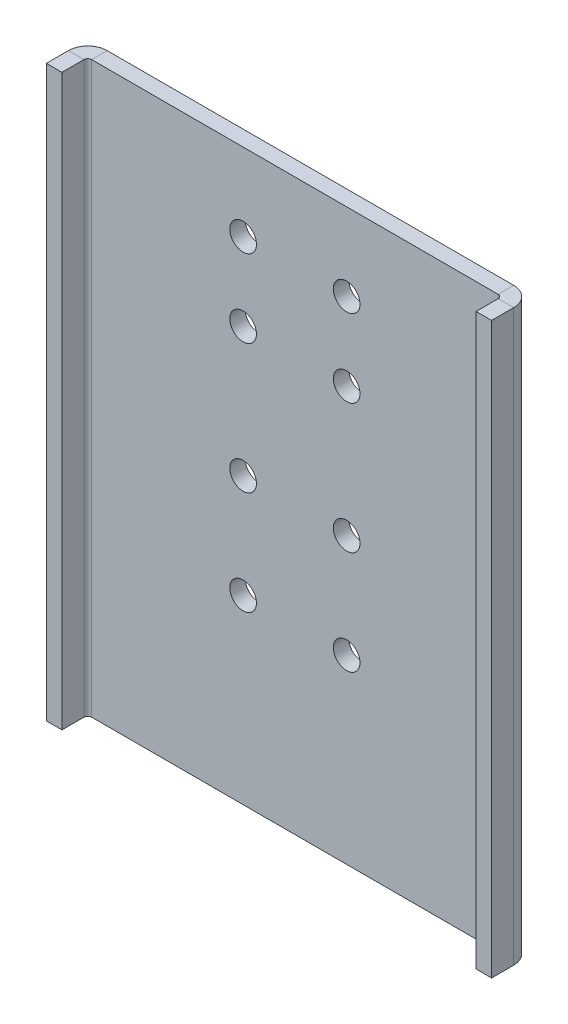
SolidWorks part; units mm, degrees
note: The reader was unsure of these and kept them because the rebuilt part matched: thickness of "Base-Flange1", "Edge-Flange1", "Sheet-Metal1", "Sheet-Metal2", "Sheet-Metal3"; flange length of "Edge-Flange1".
ref_plane "Front Plane" through (0, 0, 0) normal (0, 0, 1) x (1, 0, 0)
ref_plane "Top Plane" through (0, 0, 0) normal (0, 1, 0) x (1, 0, 0)
ref_plane "Right Plane" through (0, 0, 0) normal (1, 0, 0) x (0, 0, -1)
sketch "Sketch1" plane through (0, 0, 0) normal (0, 0, 1) x (1, 0, 0)
  line L1 (-43, 55) -> (43, 55)
  line L2 (-43, 55) -> (-43, -55)
  line L3 (-43, -55) -> (43, -55)
  line L4 (43, 55) -> (43, -55)
  line L5 (-43, 55) -> (43, -55) construction
  line L6 (-43, -55) -> (43, 55) construction
  point P0 (0, 0)
  dimension "D1" = 86
  dimension "D2" = 110
base flange "Base-Flange1" sketch "Sketch1" thickness 3 reverse thickness direction no parameters "D1"=0.7366
sketch "Sketch6" plane through (0, 0, 0) normal (0, 0, 1) x (1, 0, 0)
  line L0 (43, 55) -> (-43, 55) construction
  circle A0 centre (-10, 40) radius 2.58
  circle A1 centre (10, 40) radius 2.58
  circle A2 centre (-10, 25) radius 2.58
  circle A3 centre (10, 25) radius 2.58
  circle A4 centre (10, 0) radius 2.58
  circle A5 centre (-10, 0) radius 2.58
  circle A6 centre (-10, -20) radius 2.58
  circle A7 centre (10, -20) radius 2.58
  dimension "D7" = 5.16
  dimension "D1" = 10
  dimension "D2" = 10
  dimension "D3" = 15
  dimension "D4" = 15
  dimension "D5" = 25
  dimension "D6" = 20
extrude "Cut-Extrude1" cut sketch "Sketch6" against normal blind 3 normal cut yes
edge flange "Edge-Flange1" sketch "Sketch11" flange profiles "Sketch11", "Sketch12" flange angle 90 flange length 8 flange position material inside bend radius 0.7366 thickness 3 relief rectangular parameters "D6"=10, "D8"=0.1
sketch "Sketch11" plane through (-43, 0, 0) normal (-1, 0, 0) x (0, -1, 0)
  line L0 (-55, 0) -> (55, 0) construction
  line L1 (-55, 0) -> (55, 0)
  line L2 (-55, 0) -> (-55, 5)
  line L3 (-55, 5) -> (55, 5)
  line L4 (55, 5) -> (55, 0)
sketch "Sketch12" plane through (43, 0, 0) normal (1, 0, 0) x (0, 1, 0)
  line L0 (-55, 0) -> (55, 0) construction
  line L1 (-55, 0) -> (55, 0)
  line L2 (-55, 0) -> (-55, 5)
  line L3 (-55, 5) -> (55, 5)
  line L4 (55, 5) -> (55, 0)
bend "EdgeBend1" bend radius 0.7366 bend angle 90 parameters "D5"=1
bend "EdgeBend2" bend radius 0.7366 bend angle 90 parameters "D5"=2
sketch "Bend-Lines1" [suppressed] plane through (0, 0, 0) normal (0, 1, 0) x (1, 0, 0)
sketch "Bounding-Box1" [suppressed] plane through (0, 0, 0) normal (0, 1, 0) x (1, 0, 0)
sheet metal parameters "Sheet-Metal1" thickness 3 parameters "D1"=0.7366, "D7"=1
flat pattern "Flat-Pattern1" [suppressed]
sketch "Bend-Lines2" plane through (0, 0, 0) normal (0, 1, 0) x (1, 0, 0)
sketch3d "Bounding-Box2" [suppressed]
  line L0 (-42, 55, 0) -> (-42, -55, 0) construction
  line L1 (42, 55, 0) -> (42, -55, 0) construction
  line L2 (-42, 55, 0) -> (42, 55, 0) construction
  line L3 (-42, -55, 0) -> (42, -55, 0) construction
sheet metal parameters "Sheet-Metal2" thickness 3 parameters "D1"=0.7366, "D7"=1
flat pattern "Flat-Pattern1"
sketch "Bend-Lines2" plane through (0, 0, 0) normal (0, 1, 0) x (1, 0, 0)
sketch3d "Bounding-Box2" [suppressed]
  line L0 (42, 55, 0) -> (42, -55, 0) construction
  line L1 (-42, 55, 0) -> (-42, -55, 0) construction
  line L2 (42, 55, 0) -> (-42, 55, 0) construction
  line L3 (42, -55, 0) -> (-42, -55, 0) construction
sheet metal parameters "Sheet-Metal3" thickness 3 parameters "D1"=0.7366, "D7"=1
flat pattern "Flat-Pattern1"
sketch "Bend-Lines2" plane through (0, 0, 0) normal (0, 0, 1) x (1, 0, 0)
  line L0 (41.02, -55) -> (41.02, 55) construction
  line L1 (-41.02, 55) -> (-41.02, -55) construction
  line L2 (41.02, -55) -> (41.02, 55) construction
  line L3 (-41.02, 55) -> (-41.02, -55) construction
sketch3d "Bounding-Box2" [suppressed]
  line L0 (47.04, 55, 0) -> (47.04, -55, 0) construction
  line L1 (-47.04, 55, 0) -> (-47.04, -55, 0) construction
  line L2 (47.04, 55, 0) -> (-47.04, 55, 0) construction
  line L3 (47.04, -55, 0) -> (-47.04, -55, 0) construction
bend of the flat pattern "Flatten-<EdgeBend1>1"
bend of the flat pattern "Flatten-<EdgeBend2>1"
